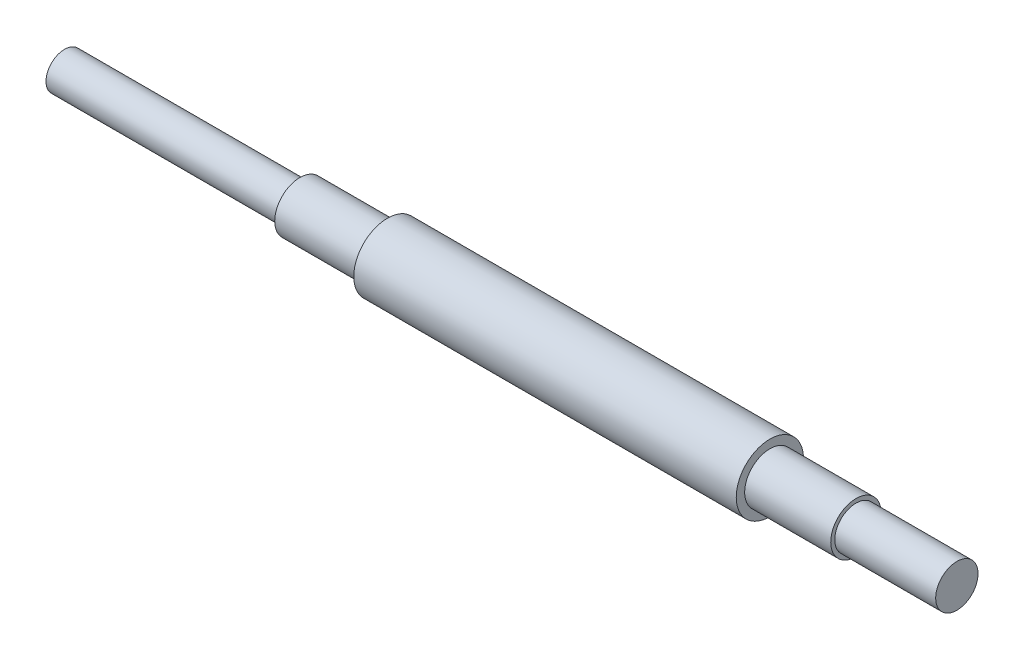
SolidWorks part; units mm, degrees
material "Plain Carbon Steel"
ref_plane "Front Plane" through (0, 0, 0) normal (0, 0, 1) x (1, 0, 0)
ref_plane "Top Plane" through (0, 0, 0) normal (0, 1, 0) x (1, 0, 0)
ref_plane "Right Plane" through (0, 0, 0) normal (1, 0, 0) x (0, 0, -1)
sketch "Sketch1" plane through (0, 0, 0) normal (0, 1, 0) x (1, 0, 0)
  line L0 (-78.6306, 0) -> (89.8554, 0) construction
  line L1 (-78.6306, 0) -> (-78.6306, 3.5)
  line L2 (-78.6306, 3.5) -> (-34.1806, 3.5)
  line L3 (-34.1806, 3.5) -> (-34.1806, 4.7625)
  line L4 (-34.1806, 4.7625) -> (-17.6706, 4.7625)
  line L5 (-17.6706, 4.7625) -> (-17.6706, 6.35)
  line L6 (-17.6706, 6.35) -> (54.5494, 6.35)
  line L7 (54.5494, 6.35) -> (54.5494, 4.7625)
  line L8 (54.5494, 4.7625) -> (70.8054, 4.7625)
  line L9 (70.8054, 4.7625) -> (70.8054, 3.9992)
  line L10 (70.8054, 3.9992) -> (89.8554, 3.9992)
  line L11 (89.8554, 3.9992) -> (89.8554, 0)
  line L12 (-78.6306, 0) -> (89.8554, 0)
  line L13 (-97.9506, 0) -> (194.5593, 0) construction
  dimension "D1" = 7
  dimension "D2" = 9.525
  dimension "D3" = 9.525
  dimension "D4" = 7.9985
  dimension "D5" = 44.45
  dimension "D6" = 16.51
  dimension "D7" = 16.256
  dimension "D8" = 19.05
  dimension "D9" = 72.22
  dimension "D10" = 6.35
revolve "Revolve1" add sketch "Sketch1" angle 360 about L13
